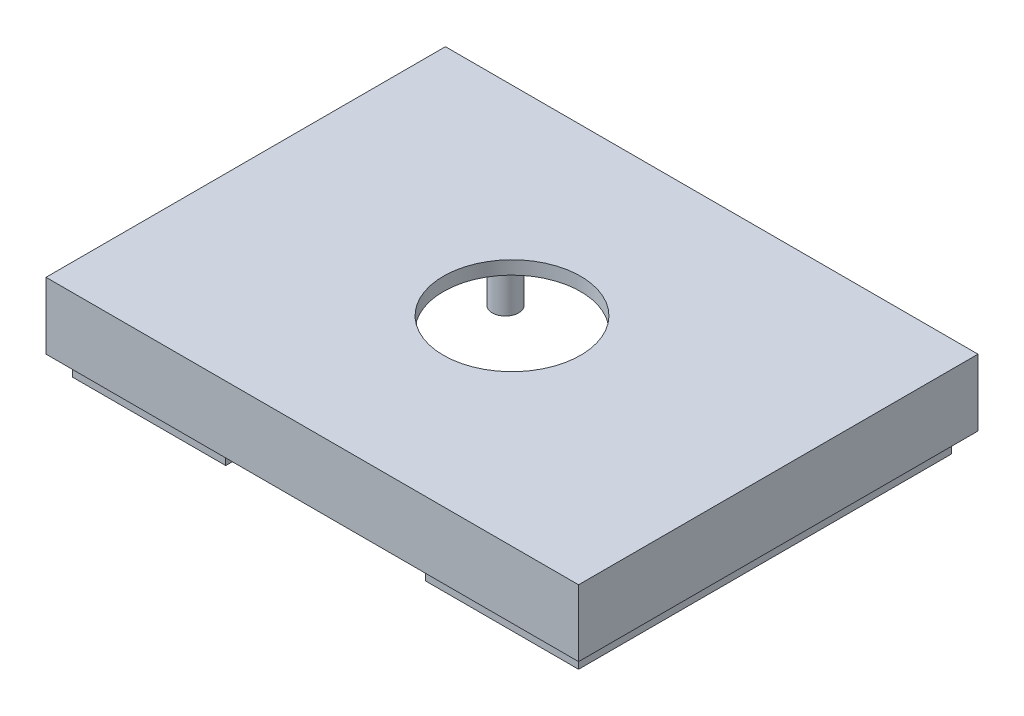
SolidWorks part; units mm, degrees
ref_plane "Front Plane" through (0, 0, 0) normal (0, 0, 1) x (1, 0, 0)
ref_plane "Top Plane" through (0, 0, 0) normal (0, 1, 0) x (1, 0, 0)
ref_plane "Right Plane" through (0, 0, 0) normal (1, 0, 0) x (0, 0, -1)
sketch "Sketch1" plane through (0, 0, 0) normal (0, 1, 0) x (1, 0, 0)
  line L1 (-50.8, 38.1) -> (50.8, 38.1)
  line L2 (-50.8, 38.1) -> (-50.8, -38.1)
  line L3 (-50.8, -38.1) -> (50.8, -38.1)
  line L4 (50.8, 38.1) -> (50.8, -38.1)
  line L5 (-50.8, 38.1) -> (50.8, -38.1) construction
  line L6 (-50.8, -38.1) -> (50.8, 38.1) construction
  point P0 (0, 0)
  dimension "D1" = 101.6
  dimension "D2" = 76.2
extrude "Boss-Extrude1" add sketch "Sketch1" along normal blind 12.7 separate body
sketch "Sketch2" plane through (0, 0, 0) normal (0, 1, 0) x (1, 0, 0)
  line L0 (-50.8, 38.1) -> (-50.8, -38.1) construction
  line L1 (-48.26, -35.56) -> (48.26, -35.56)
  line L2 (-48.26, -35.56) -> (-48.26, 35.56)
  line L3 (-48.26, 35.56) -> (48.26, 35.56)
  line L4 (48.26, -35.56) -> (48.26, 35.56)
  line L5 (-48.26, -35.56) -> (48.26, 35.56) construction
  line L6 (-48.26, 35.56) -> (48.26, -35.56) construction
  line L7 (-50.8, -38.1) -> (50.8, -38.1) construction
  point P0 (0, 0)
  dimension "D1" = 2.54
  dimension "D2" = 2.54
extrude "Boss-Extrude2" add sketch "Sketch2" against normal blind 3.81
shell "Shell1" thickness 2.54 removed face at (0, -3.81, 0)
sketch "Sketch3" plane through (0, 0, 0) normal (0, 1, 0) x (1, 0, 0)
  line L0 (-48.26, -35.56) -> (48.26, -35.56) construction
  line L1 (-19.05, -35.56) -> (19.05, -35.56)
  line L2 (-19.05, -35.56) -> (-19.05, -33.02)
  line L3 (-19.05, -33.02) -> (19.05, -33.02)
  line L4 (19.05, -35.56) -> (19.05, -33.02)
  line L5 (-45.72, -33.02) -> (45.72, -33.02) construction
  line L6 (0, 0) -> (0, -13.3167) construction
  dimension "D1" = 38.1
extrude "Cut-Extrude1" cut sketch "Sketch3" against normal blind 3.81
sketch "Sketch5" plane through (0, 12.7, 0) normal (0, 1, 0) x (1, 0, 0)
  circle A0 centre (0, 0) radius 13.081
  dimension "D1" = 26.162
extrude "Cut-Extrude2" cut sketch "Sketch5" against normal blind 2.54
sketch "Sketch6" plane through (0, 10.16, 0) normal (0, -1, 0) x (1, 0, 0)
  line L0 (-19.05, 0) -> (19.05, 0) construction
  line L1 (0, 15.0526) -> (0, -15.0526) construction
  circle A0 centre (-12.4968, 9.2456) radius 1.5
  circle A1 centre (0, 0) radius 13.081 construction
  circle A2 centre (13.9954, 9.2456) radius 1.5
  circle A3 centre (13.9954, -11.2522) radius 1.5
  circle A4 centre (-12.4968, -11.2522) radius 1.5
  point P5 (0, 0)
  point P9 (0, 0)
  point P15 (0, 0)
  point P20 (0, 0)
  point P21 (0, 0)
  point P22 (0, 0)
  point P23 (0, 0)
  dimension "D1" = 12.4968
  dimension "D2" = 13.9954
  dimension "D3" = 11.2522
  dimension "D4" = 9.2456
  dimension "D5" = 3
extrude "Extrude-Thin1" add sketch "Sketch6" along normal blind 7.62 thin thin type one direction wall 1.016
extrude "Cut-Extrude3" cut sketch "Sketch6<2>" against normal blind 1.27
sketch "Sketch6<2>" plane through (0, 10.16, 0) normal (0, -1, 0) x (1, 0, 0) same geometry as "Sketch6"
thread "Thread1" pitch 0.5 method extrude profile "Thread Profile2" start angle 0, offset 0, length 6.35, pitch 0.5, diameter 3
ref_plane "Plane2" through (-10.9968, 2.54, 9.2456) normal (0, 0, 1) x (1, 0, 0)
sketch "Thread Profile2" plane through (-10.9968, 2.54, 9.2456) normal (0, 0, 1) x (1, 0, 0)
  line L0 (0, 0) -> (0, 0.5) construction
  line L11 (0, 0) -> (0, 0.4375)
  line L12 (0, 0.4375) -> (-0.2706, 0.2812)
  line L13 (-0.2706, 0.2812) -> (-0.2706, 0.1562)
  line L15 (-0.2706, 0.1562) -> (0, 0)
  line L17 (-0.2706, 0.2187) -> (0, 0.2187) construction
  point P2 (0, 0)
  dimension "Pitch" = 0.5
  dimension "Profile_Angle" = 60
  dimension "Profile_Land" = 0.125
  dimension "Profile_Height" = 0.2706
thread "Thread2" pitch 0.5 method extrude profile "Thread Profile3" start angle 0, offset 0, length 6.35, pitch 0.5, diameter 3
ref_plane "Plane3" through (15.4954, 2.54, -11.2522) normal (0, 0, 1) x (1, 0, 0)
sketch "Thread Profile3" plane through (15.4954, 2.54, -11.2522) normal (0, 0, 1) x (1, 0, 0)
  line L0 (0, 0) -> (0, 0.5) construction
  line L11 (0, 0) -> (0, 0.4375)
  line L12 (0, 0.4375) -> (-0.2706, 0.2812)
  line L13 (-0.2706, 0.2812) -> (-0.2706, 0.1562)
  line L15 (-0.2706, 0.1562) -> (0, 0)
  line L17 (-0.2706, 0.2187) -> (0, 0.2187) construction
  point P2 (0, 0)
  dimension "Pitch" = 0.5
  dimension "Profile_Angle" = 60
  dimension "Profile_Land" = 0.125
  dimension "Profile_Height" = 0.2706
thread "Thread3" pitch 0.5 method extrude profile "Thread Profile4" start angle 0, offset 0, length 6.35, pitch 0.5, diameter 3
ref_plane "Plane4" through (15.4954, 2.54, 9.2456) normal (0, 0, 1) x (1, 0, 0)
sketch "Thread Profile4" plane through (15.4954, 2.54, 9.2456) normal (0, 0, 1) x (1, 0, 0)
  line L0 (0, 0) -> (0, 0.5) construction
  line L11 (0, 0) -> (0, 0.4375)
  line L12 (0, 0.4375) -> (-0.2706, 0.2812)
  line L13 (-0.2706, 0.2812) -> (-0.2706, 0.1562)
  line L15 (-0.2706, 0.1562) -> (0, 0)
  line L17 (-0.2706, 0.2187) -> (0, 0.2187) construction
  point P2 (0, 0)
  dimension "Pitch" = 0.5
  dimension "Profile_Angle" = 60
  dimension "Profile_Land" = 0.125
  dimension "Profile_Height" = 0.2706
thread "Thread4" pitch 0.5 method extrude profile "Thread Profile5" start angle 0, offset 0, length 6.35, pitch 0.5, diameter 3
ref_plane "Plane5" through (-10.9968, 2.54, -11.2522) normal (0, 0, 1) x (1, 0, 0)
sketch "Thread Profile5" plane through (-10.9968, 2.54, -11.2522) normal (0, 0, 1) x (1, 0, 0)
  line L0 (0, 0) -> (0, 0.5) construction
  line L11 (0, 0) -> (0, 0.4375)
  line L12 (0, 0.4375) -> (-0.2706, 0.2812)
  line L13 (-0.2706, 0.2812) -> (-0.2706, 0.1562)
  line L15 (-0.2706, 0.1562) -> (0, 0)
  line L17 (-0.2706, 0.2187) -> (0, 0.2187) construction
  point P2 (0, 0)
  dimension "Pitch" = 0.5
  dimension "Profile_Angle" = 60
  dimension "Profile_Land" = 0.125
  dimension "Profile_Height" = 0.2706
equation "\"`1.03\"=0.103"
